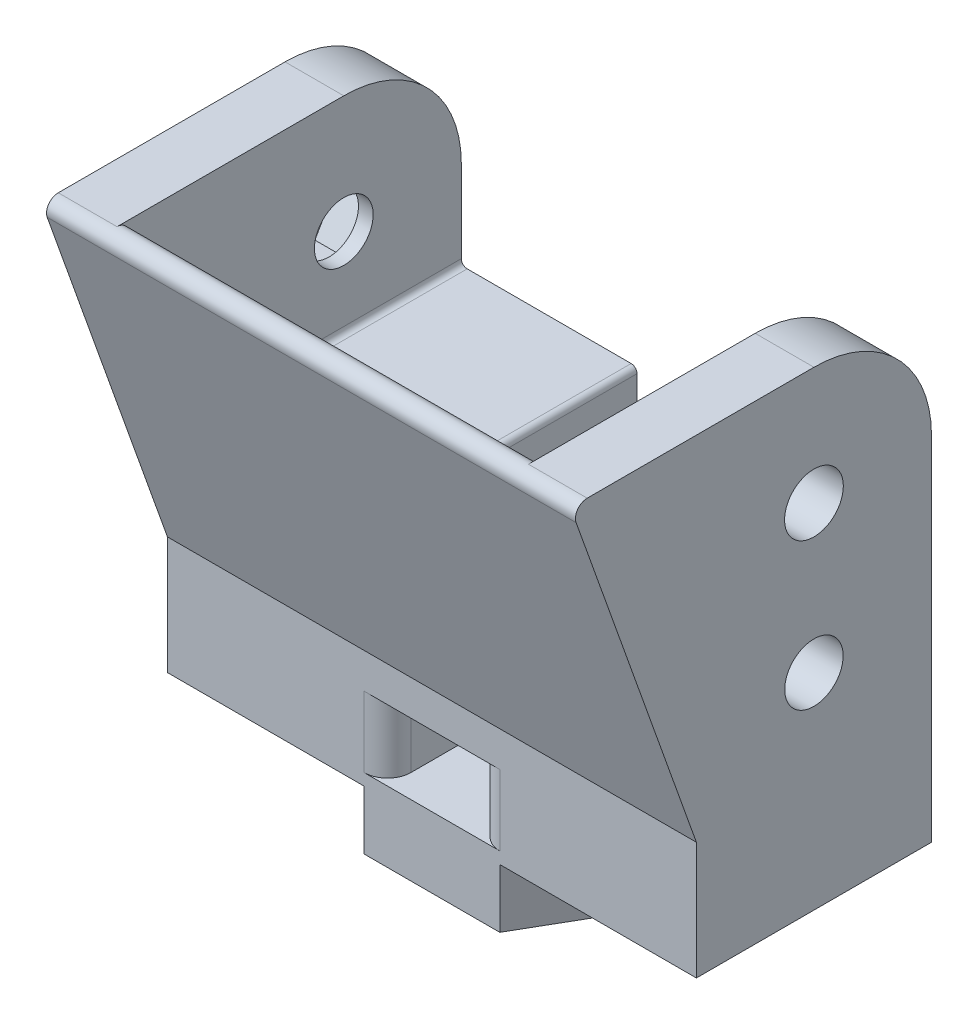
SolidWorks part; units mm, degrees
material "ABS"
ref_plane "Front Plane" through (0, 0, 0) normal (0, 0, 1) x (1, 0, 0)
ref_plane "Top Plane" through (0, 0, 0) normal (0, 1, 0) x (1, 0, 0)
ref_plane "Right Plane" through (0, 0, 0) normal (1, 0, 0) x (0, 0, -1)
sketch "Sketch2" plane through (0, 0, 0) normal (1, 0, 0) x (0, 0, -1)
  line L0 (0, 0) -> (0, 25.4)
  line L1 (25.4, 0) -> (25.4, 25.4)
  line L2 (25.4, 0) -> (0, 0)
  line L3 (0, 24.4853) -> (-10.8181, 37.6368)
  line L4 (-12.995, 36.403) -> (0, 0)
  line L6 (12.7, 38.1) -> (-11.7989, 38.1)
  circle A0 centre (12.7, 25.4) radius 12.7
  circle A1 centre (12.7, 25.4) radius 3.175
  circle A2 centre (12.7, 9.525) radius 3.1559
  arc A4 (-10.8181, 37.6368) -> (-12.995, 36.403) centre (-11.7989, 36.83) ccw
  dimension "D1" = 25.4
  dimension "D5" = 6.35
  dimension "D6" = 6.3119
  dimension "D8" = 0.9147
  dimension "D13" = 2.54
  dimension "D2" = 25.4
  dimension "D4" = 140.56
  dimension "D7" = 15.875
extrude "Boss-Extrude1" add sketch "Sketch2" along normal blind 57.15 contours L3 A4 L4 L0 | A0 L0 L2 L1 A2 | A0 A1 region at (0, 21.9286, 4.8322) region at (0, 12.2427, -0.3592) region at (0, 34.1263, -3.9737)
sketch "Sketch3" plane through (0, 0, -25.4) normal (0, 0, -1) x (-1, 0, 0)
  line L0 (-50.8, 38.1) -> (-50.8, 0)
  line L1 (-50.8, 0) -> (-6.35, 0)
  line L2 (-6.35, 0) -> (-6.35, 38.1)
  line L5 (-57.15, 0) -> (0, 0) construction
  line L6 (-50.8, 38.1) -> (-6.35, 38.1)
  line L7 (0, 38.1) -> (-57.15, 38.1) construction
  line L9 (-50.8, 15.875) -> (-31.8135, 15.875)
  line L10 (-50.8, 15.875) -> (-50.8, 0)
  line L11 (-50.8, 0) -> (-31.8135, 0)
  line L12 (-31.8135, 15.875) -> (-31.8135, 0)
  line L13 (-6.35, 15.875) -> (-25.3365, 15.875)
  line L14 (-6.35, 15.875) -> (-6.35, 0)
  line L15 (-6.35, 0) -> (-25.3365, 0)
  line L16 (-25.3365, 15.875) -> (-25.3365, 0)
  line L18 (-57.15, 0) -> (-57.15, 25.4) construction
  point P20 (-31.8135, 7.9375)
  point P21 (-25.3365, 7.9375)
  line M6 (0, 25.4) -> (-57.15, 25.4)
  dimension "D1" = 6.477
  dimension "D2" = 6.35
  dimension "D4" = 18.9865
  dimension "D5" = 15.875
extrude "Hollowing" cut sketch "Sketch3" against normal blind 25.4 contours L16 L13 L2 L0 L9 L12 L1 M6 | L6 L0 L2 M6 region at (28.575, 18.1559, -25.4) region at (28.575, 31.75, -25.4)
fillet "Fillet2" radius 0.635 4 edges at (31.8135, 15.875, -12.7) (6.35, 15.875, -12.7) (25.3365, 15.875, -12.7) (50.8, 15.875, -12.7) tangent propagation no
sketch "Sketch8" plane through (25.3365, 0, 0) normal (1, 0, 0) x (0, 0, -1)
  line L0 (1.3585, 15.24) -> (0, 15.24)
  line L4 (25.4, 0) -> (25.4, 15.24)
  line L5 (25.4, 15.24) -> (0, 15.24)
  line L6 (0, 15.24) -> (0, 0)
  line L7 (0, 0) -> (25.4, 0)
  line L8 (25.4, 0) -> (25.4, 15.24)
  line L9 (25.4, 15.24) -> (24.0415, 15.24)
  line L10 (0, 15.24) -> (0, 0)
  line L11 (0, 0) -> (25.4, 0)
  arc A0 (1.3585, 15.24) -> (24.0415, 15.24) centre (12.7, 9.525) ccw
  circle A1 centre (12.7, 9.525) radius 3.156 construction
  arc A2 (21.1003, 0) -> (24.0415, 15.24) centre (12.7, 9.525) ccw
  line M12 (0, 0) -> (25.4, 0)
  dimension "D1" = 0
extrude "Gear Crevase" add sketch "Sketch8" along normal up to surface (6.477 mm away) contours A0 L10 M12 region at (25.3365, 2.2931, -1.2414) up to face at (31.8135, 9.525, -15.8559)
sketch "Sketch4" plane through (0, 0, 0) normal (0, -1, 0) x (1, 0, 0)
  line L6 (0, 0) -> (57.15, 0)
  line L7 (0, 0) -> (0, -25.4)
  line L8 (0, -25.4) -> (57.15, -25.4)
  line L9 (57.15, 0) -> (57.15, -25.4)
  line L11 (0, 0) -> (57.15, -25.4) construction
  line L12 (0, -25.4) -> (57.15, 0) construction
  point P4 (28.575, -12.7)
  line M6 (31.8135, -4.2997) -> (31.8135, -25.4)
  line M7 (31.8135, -25.4) -> (57.15, -25.4)
extrude "Base Extension" add sketch "Sketch4" along normal blind 12.7 contours L7 M7 M6 | L9 L6 L8 M6 region at (28.575, 0, -12.7)
sketch "Sketch5" plane through (0, -12.7, 0) normal (0, -1, 0) x (1, 0, 0)
  line L1 (0, -25.4) -> (57.15, -25.4) construction
  line L2 (35.9073, 0) -> (21.2427, 0)
  line L4 (21.2427, 0) -> (13.9103, -12.7)
  line L5 (13.9103, -12.7) -> (21.2427, -25.4)
  line L6 (21.2427, -25.4) -> (35.9073, -25.4)
  line L7 (35.9073, -25.4) -> (43.2397, -12.7)
  line L8 (43.2397, -12.7) -> (35.9073, 0)
  line L9 (0, 0) -> (0, -25.4) construction
  circle A3 centre (28.575, -12.7) radius 12.7 construction
  point P14 (0, -12.7)
  point P17 (28.575, -25.4)
  dimension "D1" = 25.4
sketch "Sketch7" plane through (0, 0, 0) normal (-1, 0, 0) x (0, 0, 1)
  line L0 (-12.7, 25.4) -> (-12.7, 30.9943) construction
  line L1 (-9.4701, 19.8056) -> (-6.2402, 25.4)
  line L2 (-6.2402, 25.4) -> (-9.4701, 30.9943)
  line L3 (-9.4701, 30.9943) -> (-15.9299, 30.9943)
  line L4 (-15.9299, 30.9943) -> (-19.1598, 25.4)
  line L5 (-19.1598, 25.4) -> (-15.9299, 19.8056)
  line L6 (-15.9299, 19.8056) -> (-9.4701, 19.8056)
  circle A0 centre (-12.7, 25.4) radius 5.5943 construction
  dimension "D1" = 11.1887
extrude "Captive Nut Bore" cut sketch "Sketch7" against normal blind 4.7625
extrude "Hex Connection" add sketch "Sketch5" along normal blind 6.35
extrude "Gear Clearance" cut sketch "Sketch8<3>" along normal up to surface (6.477 mm away) contours L11 A0 region at (25.3365, -1.2847, -12.7) up to face at (31.8135, 9.525, -15.8559)
sketch "Sketch8<3>" plane through (25.3365, 0, 0) normal (1, 0, 0) x (0, 0, -1) same geometry as "Sketch8"
extrude "Boss-Extrude6" add sketch "Sketch2<3>" along normal up to surface (6.35 mm away) contours A4 L3 A0 L6 region at (0, 34.0948, 1.6859) up to face at (6.35, 22.225, -12.7)
sketch "Sketch2<3>" plane through (0, 0, 0) normal (1, 0, 0) x (0, 0, -1) same geometry as "Sketch2"
extrude "Boss-Extrude7" add sketch "Sketch2<4>" along normal up to surface (57.15 mm away) from surface contours A4 L3 A0 L6 region at (0, 34.0948, 1.6859) up to face at (57.15, 17.1925, -3.3085) starting at face at (50.8, 28.575, -12.7)
sketch "Sketch2<4>" plane through (0, 0, 0) normal (1, 0, 0) x (0, 0, -1) same geometry as "Sketch2"
sketch "Sketch9" plane through (0, 0, 0) normal (0, 0, 1) x (1, 0, 0)
  line L0 (28.575, -19.05) -> (28.575, -7.62) construction
  line L1 (33.3756, -11.43) -> (23.7744, -11.43)
  line L2 (33.3756, -11.43) -> (33.3756, -3.81)
  line L3 (33.3756, -3.81) -> (23.7744, -3.81)
  line L4 (23.7744, -11.43) -> (23.7744, -3.81)
  line L5 (33.3756, -11.43) -> (23.7744, -3.81) construction
  line L6 (33.3756, -3.81) -> (23.7744, -11.43) construction
  line L7 (35.9073, -19.05) -> (21.2427, -19.05) construction
  point P4 (28.575, -7.62)
  dimension "D1" = 7.62
  dimension "D2" = 9.6012
  dimension "D3" = 11.43
extrude "Cut-Extrude5" cut sketch "Sketch9" against normal blind 11.43
sketch "Sketch10" plane through (0, -19.05, 0) normal (0, -1, 0) x (1, 0, 0)
  line L0 (57.15, 0) -> (0, 0) construction
  line L1 (28.575, -7.1567) -> (23.7744, -9.9284)
  line L2 (23.7744, -9.9284) -> (23.7744, -15.4716)
  line L3 (23.7744, -15.4716) -> (28.575, -18.2433)
  line L4 (28.575, -18.2433) -> (33.3756, -15.4716)
  line L5 (33.3756, -15.4716) -> (33.3756, -9.9284)
  line L6 (33.3756, -9.9284) -> (28.575, -7.1567)
  circle A0 centre (28.575, -12.7) radius 4.8006 construction
  point P13 (28.575, 0)
  dimension "D1" = 9.6012
extrude "Cut-Extrude6" cut sketch "Sketch10" against normal up to surface (15.24 mm away) from surface up to face at (28.575, -3.81, -5.715) starting at face at (28.575, -11.43, -5.715)
hole_wizard "#10 (0.1935) Diameter Hole1" positions "Sketch12" profile "Sketch13" hole size "#10" standard "ANSI Inch" end condition up to next
sketch "Sketch12" plane through (0, -19.05, 0) normal (0, -1, 0) x (-1, 0, 0)
  line L0 (-21.2427, 25.4) -> (-35.9073, 25.4) construction
  point P0 (-28.575, 12.7)
  point P6 (-28.575, 25.4)
sketch "Sketch13" plane through (28.575, -19.05, -12.7) normal (1, 0, 0) x (0, 0, -1)
  line L0 (0, 0) -> (0, 7.62)
  line L1 (0, 7.62) -> (2.5209, 7.62)
  line L2 (2.5209, 7.62) -> (2.5209, 0)
  line L5 (2.5209, 0) -> (0, 0)
  line L11 (0, -6.35) -> (0, 107.95) construction
  dimension "Thru Hole Dia." = 5.0419
  dimension "Thru Hole Depth" = 7.62
fillet "Fillet3" radius 2.54 2 edges at (33.3756, -7.62, 0) (23.7744, -7.62, 0)
sketch "Sketch14" plane through (0, 0, 0) normal (-1, 0, 0) x (0, 0, 1)
  circle A0 centre (-12.7, 9.525) radius 4.6673
  circle A1 centre (-12.7, 9.525) radius 3.156 construction
  dimension "D1" = 9.3345
extrude "Cut-Extrude7" cut sketch "Sketch14" against normal blind 3.175
ref_plane "Plane1" through (28.575, 0, 0) normal (-1, 0, 0) x (0, 0, 1)
